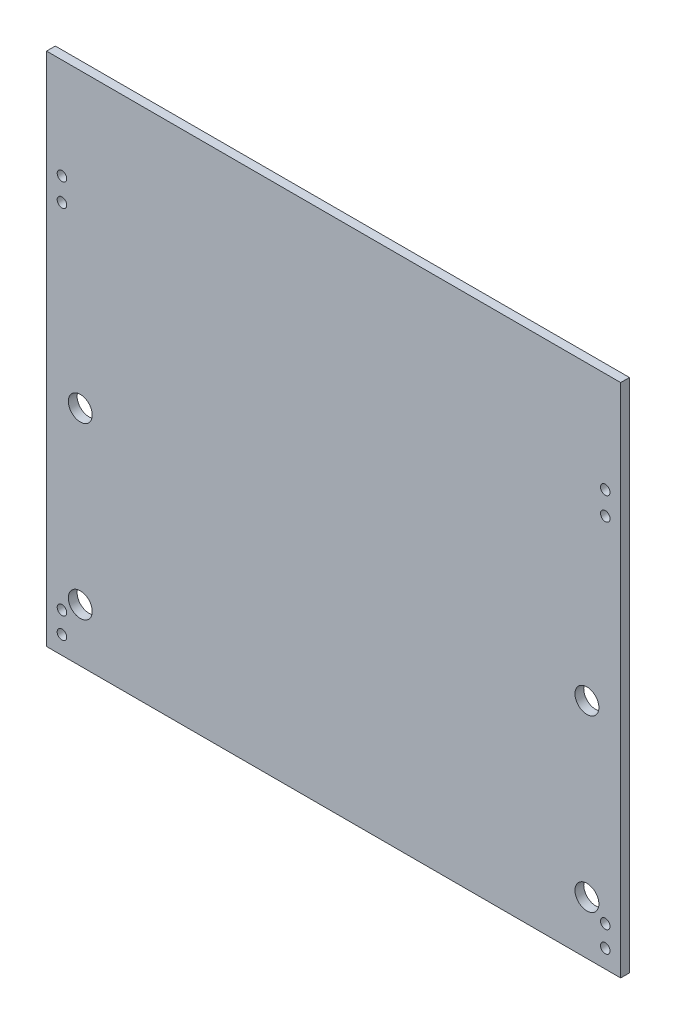
SolidWorks part; units mm, degrees
ref_plane "Front Plane" through (0, 0, 0) normal (0, 0, 1) x (1, 0, 0)
ref_plane "Top Plane" through (0, 0, 0) normal (0, 1, 0) x (1, 0, 0)
ref_plane "Right Plane" through (0, 0, 0) normal (1, 0, 0) x (0, 0, -1)
sketch "Sketch1" plane through (0, 0, 0) normal (0, 0, 1) x (1, 0, 0)
  line L1 (-73.1533, 40.2838) -> (142.8467, 40.2838)
  line L2 (-73.1533, 40.2838) -> (-73.1533, -153.7162)
  line L3 (-73.1533, -153.7162) -> (142.8467, -153.7162)
  line L4 (142.8467, 40.2838) -> (142.8467, -153.7162)
  circle A0 centre (-67.3533, -146.9162) radius 1.8
  circle A1 centre (-67.3533, -138.9162) radius 1.8
  circle A2 centre (-67.3533, -6.1162) radius 1.8
  circle A3 centre (137.0467, 2.4838) radius 1.8
  circle A4 centre (137.0467, -146.9162) radius 1.8
  circle A5 centre (137.0467, -138.9162) radius 1.8
  circle A6 centre (137.0467, -6.1162) radius 1.8
  circle A7 centre (-67.3533, 2.4838) radius 1.8
  circle A8 centre (-60.4533, -133.7162) radius 4.5
  circle A9 centre (130.1467, -133.7162) radius 4.5
  circle A10 centre (-60.4533, -69.7162) radius 4.5
  circle A11 centre (130.1467, -69.7162) radius 4.5
  dimension "D3" = 6.8
  dimension "D11" = 12.7
  dimension "D13" = 12.7
  dimension "D15" = 64
  dimension "D16" = 64
  dimension "D17" = 12.7
  dimension "D1" = 216
  dimension "D2" = 194
  dimension "D4" = 8
  dimension "D5" = 5.8
  dimension "D6" = 37.8
  dimension "D7" = 5.8
  dimension "D8" = 5.8
  dimension "D9" = 46.4
  dimension "D10" = 5.8
  dimension "D12" = 20
  dimension "D14" = 20
  dimension "D18" = 12.7
extrude "Boss-Extrude1" add sketch "Sketch1" along normal blind 3.302
